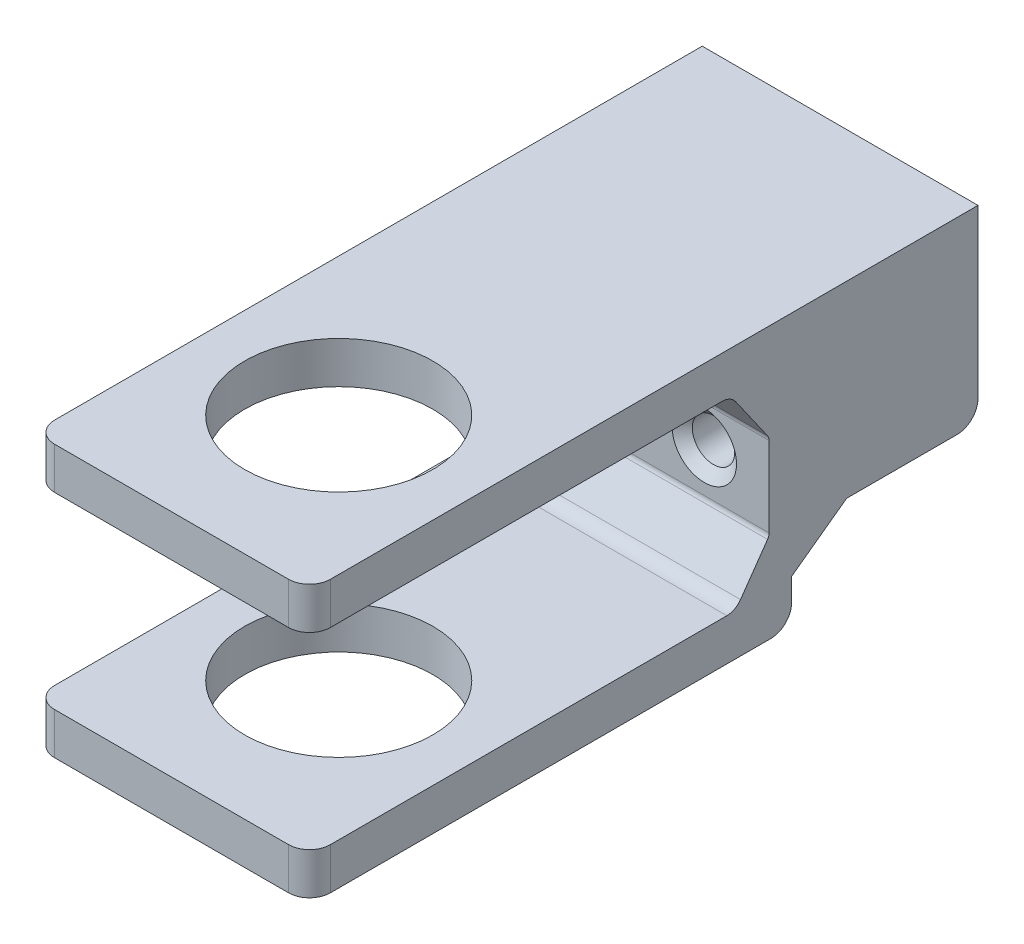
SolidWorks part; units mm, degrees
ref_plane "Front Plane" through (0, 0, 0) normal (0, 0, 1) x (1, 0, 0)
ref_plane "Top Plane" through (0, 0, 0) normal (0, 1, 0) x (1, 0, 0)
ref_plane "Right Plane" through (0, 0, 0) normal (1, 0, 0) x (0, 0, -1)
sketch "Sketch1" plane through (0, 0, 0) normal (0, 1, 0) x (1, 0, 0)
  line L1 (-20.955, -50.8) -> (20.955, -50.8)
  line L2 (-20.955, -50.8) -> (-20.955, 50.8)
  line L3 (-20.955, 50.8) -> (20.955, 50.8)
  line L4 (20.955, -50.8) -> (20.955, 50.8)
  line L5 (-20.955, -50.8) -> (20.955, 50.8) construction
  line L6 (-20.955, 50.8) -> (20.955, -50.8) construction
  point P0 (0, 0)
  dimension "D1" = 41.91
  dimension "D2" = 101.6
extrude "Boss-Extrude1" add sketch "Sketch1" along normal blind 41.275
sketch "Sketch13" plane through (-20.955, 0, 0) normal (-1, 0, 0) x (0, 0, 1)
  line L0 (-19.05, 26.6024) -> (-13.2225, 34.925)
  line L1 (-13.2225, 34.925) -> (50.8, 34.925)
  line L2 (-19.05, 26.6024) -> (-19.05, 13.6323)
  line L3 (-13.9509, 6.35) -> (50.8, 6.35)
  line L4 (-50.8, 0) -> (50.8, 0)
  line L5 (50.8, 0) -> (50.8, 41.275)
  line L6 (50.8, 41.275) -> (-50.8, 41.275)
  line L7 (-50.8, 41.275) -> (-50.8, 0)
  line L8 (-50.8, 0) -> (50.8, 0)
  line L9 (50.8, 0) -> (50.8, 41.275)
  line L10 (50.8, 41.275) -> (-50.8, 41.275)
  line L11 (-50.8, 41.275) -> (-50.8, 0)
  line L12 (50.8, 34.925) -> (50.8, 6.35)
  line L13 (-19.05, 13.6323) -> (-13.9509, 6.35)
  line M11 (50.8, 0) -> (50.8, 41.275)
  dimension "D2" = 6.35
  dimension "D3" = 31.75
  dimension "D4" = 6.35
  dimension "D5" = 10.16
  dimension "D6" = 125
  dimension "D7" = 8.89
  dimension "D8" = 64.0225
  dimension "D9" = 125
  dimension "D1" = 0
extrude "Cut-Extrude6" cut sketch "Sketch13" against normal through all contours L2 L13 L3 L1 L0 M11 region at (-20.955, 20.6073, 16.6003)
sketch "Sketch3" plane through (0, 41.275, 0) normal (0, 1, 0) x (1, 0, 0)
  line L1 (20.955, 50.8) -> (-20.955, 50.8) construction
  line L3 (2.7496, -20.6375) -> (-2.7496, -20.6375)
  line L4 (-2.7496, -20.6375) -> (-5.4993, -25.4)
  line L5 (-5.4993, -25.4) -> (-2.7496, -30.1625)
  line L6 (-2.7496, -30.1625) -> (2.7496, -30.1625)
  line L7 (2.7496, -30.1625) -> (5.4993, -25.4)
  line L8 (5.4993, -25.4) -> (2.7496, -20.6375)
  circle A0 centre (0, -25.4) radius 50.8
  circle A1 centre (0, -25.4) radius 4.7625 construction
  circle A2 centre (0, -25.4) radius 14.3002
  dimension "D1" = 101.6
  dimension "D2" = 25.4
  dimension "D3" = 9.525
  dimension "D4" = 28.6004
extrude "Cut-Extrude2" cut sketch "Sketch3" against normal through all contours L7 L8 L3 L4 L5 L6 | A2 L8 L7 L6 L5 L4 L3 region at (0, 41.275, 25.4) region at (-13.8957, 41.275, 25.4)
sketch "Sketch17" plane through (-20.955, 0, 0) normal (-1, 0, 0) x (0, 0, 1)
  line L0 (-30.8359, 12.7) -> (-22.479, 6.6084)
  line L11 (-50.8, 41.275) -> (-50.8, 0) construction
  line L16 (-50.8, 0) -> (-22.479, 0)
  line L17 (-50.8, 0) -> (-50.8, 12.7)
  line L18 (-50.8, 12.7) -> (-30.8359, 12.7)
  line L19 (-22.479, 0) -> (-22.479, 6.6084)
  line L20 (-50.8, 0) -> (50.8, 0) construction
  dimension "D1" = 28.321
  dimension "D2" = 12.7
  dimension "D3" = 10.3414
  dimension "D4" = 6.6084
extrude "Cut-Extrude7" cut sketch "Sketch17" against normal through all
sketch "Sketch4" plane through (0, 0, -50.8) normal (0, 0, -1) x (-1, 0, 0)
  line L0 (-20.955, 20.6375) -> (20.955, 20.6375) construction
  line L1 (-20.955, 41.275) -> (-20.955, 12.7) construction
  line L3 (11.1125, 20.6375) -> (-11.1125, 20.6375) construction
  line L4 (-20.955, 41.275) -> (20.955, 41.275) construction
  circle A0 centre (11.1125, 20.6375) radius 3.2258
  circle A1 centre (-11.1125, 20.6375) radius 3.2258
  point P10 (0, 20.6375)
  point P12 (0, 20.6375)
  dimension "D1" = 6.4516
  dimension "D2" = 22.225
  dimension "D3" = 20.6375
  dimension "D4" = 41.91
extrude "Cut-Extrude3" cut sketch "Sketch4" against normal through all
fillet "Fillet2" radius 3.175 6 edges at (-20.955, 3.175, 50.8) (20.955, 3.175, 50.8) (-20.955, 38.1, 50.8) (20.955, 38.1, 50.8) (0, 12.7, -50.8) (0, 0, -22.479)
hole_wizard "CSK for #10 Flat Head Machine Screw (100)4" positions "Sketch14" profile "Sketch15" countersink size "#10" standard "ANSI Inch"
sketch "Sketch14" plane through (0, 0, -19.05) normal (0, 0, 1) x (1, 0, 0)
  point P0 (-11.1125, 20.6375)
  point P3 (11.1125, 20.6375)
sketch "Sketch15" plane through (-11.1125, 20.6375, -19.05) normal (1, 0, 0) x (0, -1, 0)
  line L0 (0, 0) -> (0, 33.4364)
  line L1 (0, 33.4364) -> (2.8067, 31.75)
  line L2 (2.8067, 31.75) -> (2.8067, 1.7477)
  line L3 (2.8067, 1.7477) -> (4.8895, 0)
  line L5 (4.8895, 0) -> (0, 0)
  line L6 (-2.8067, 1.7477) -> (-4.8895, 0) construction
  line L10 (0, 33.4364) -> (-2.8067, 31.75) construction
  line L11 (0, -6.35) -> (0, 107.95) construction
  dimension "Hole Dia." = 5.6134
  dimension "Hole Depth" = 31.75
  dimension "Near C'Sink Dia." = 9.779
  dimension "Near C'Sink Angle" = 100
  dimension "Drill Angle" = 118
fillet "Fillet3" radius 2.54 2 edges at (0, 6.35, -13.9509) (0, 34.925, -13.2225)
fillet "Fillet4" radius 1.27 2 edges at (0, 13.6323, -19.05) (0, 26.6024, -19.05)
